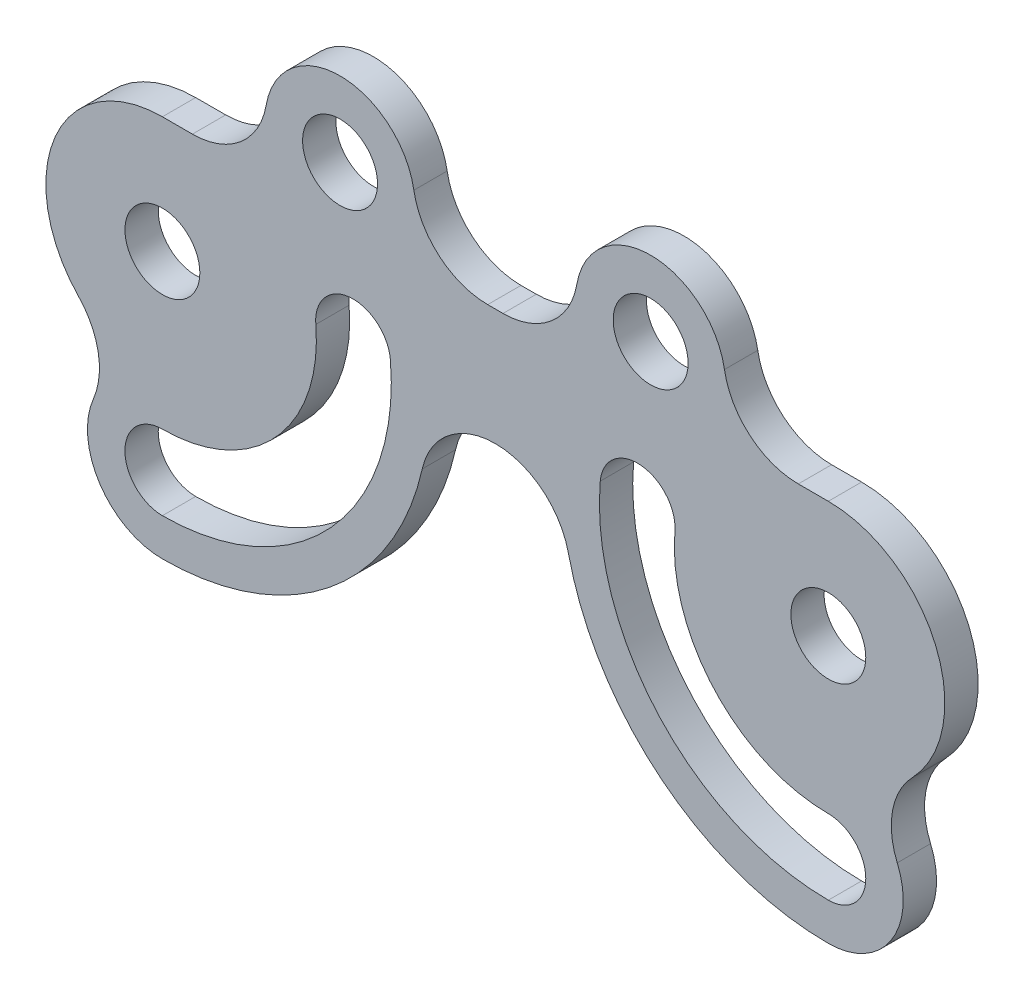
SolidWorks part; units mm, degrees
ref_plane "Front Plane" through (0, 0, 0) normal (0, 0, 1) x (1, 0, 0)
ref_plane "Top Plane" through (0, 0, 0) normal (0, 1, 0) x (1, 0, 0)
ref_plane "Right Plane" through (0, 0, 0) normal (1, 0, 0) x (0, 0, -1)
sketch "Sketch1" plane through (0, 0, 0) normal (0, 0, 1) x (1, 0, 0)
  line L14 (5.5562, 0) -> (26.1937, 0)
  line L15 (0, 5.5563) -> (31.75, 5.5563)
  line L16 (0, 5.5563) -> (0, -5.5563) construction
  line L17 (0, -5.5563) -> (31.75, -5.5563) construction
  line L18 (31.75, 5.5563) -> (31.75, -5.5563) construction
  line L19 (0, 5.5563) -> (31.75, 5.5563) construction
  line L20 (31.75, 0) -> (22.6566, 0.7956) construction
  line L21 (0, 0) -> (9.0934, 0.7956) construction
  line L22 (9.0934, 0.7956) -> (8.4708, 7.9121) construction
  line L23 (22.6566, 0.7956) -> (23.2792, 7.9121) construction
  circle A46 centre (0, 0) radius 5.5563 construction
  circle A47 centre (31.75, 0) radius 5.5563 construction
  arc A48 (0, 5.5563) -> (0, -5.5563) centre (0, 0) ccw
  arc A49 (31.75, -5.5563) -> (31.75, 5.5563) centre (31.75, 0) ccw
  circle A50 centre (0, 0) radius 1.7859
  circle A51 centre (31.75, 0) radius 1.7859
  arc A52 (0, -5.5563) -> (5.5562, 0) centre (0, 0) ccw
  arc A53 (26.1937, 0) -> (31.75, -5.5563) centre (31.75, 0) ccw
  circle A54 centre (31.75, 0) radius 9.1281 construction
  circle A55 centre (0, 0) radius 9.1281 construction
  circle A56 centre (31.75, -9.1281) radius 3.5719
  circle A57 centre (0, -9.1281) radius 3.5719
  circle A58 centre (0, -9.1281) radius 1.7859
  circle A59 centre (8.4708, 7.9121) radius 1.7859
  circle A60 centre (8.4708, 7.9121) radius 3.5719
  circle A61 centre (9.0934, 0.7956) radius 1.7859
  circle A62 centre (9.0934, 0.7956) radius 3.5719 construction
  circle A63 centre (22.6566, 0.7956) radius 1.7859
  circle A64 centre (22.6566, 0.7956) radius 3.5719 construction
  circle A65 centre (23.2792, 7.9121) radius 1.7859
  circle A66 centre (23.2792, 7.9121) radius 3.5719
  circle A67 centre (31.75, -9.1281) radius 1.7859
  arc A68 (7.3142, 0.6399) -> (0, -7.3422) centre (0, 0) cw
  arc A69 (0, -12.7) -> (12.6517, 1.1069) centre (0, 0) ccw
  arc A70 (0, -10.9141) -> (10.8725, 0.9512) centre (0, 0) ccw
  arc A71 (24.4358, 0.6399) -> (31.75, -7.3422) centre (31.75, 0) ccw
  arc A72 (20.8775, 0.9512) -> (31.75, -10.9141) centre (31.75, 0) ccw
  arc A73 (19.0983, 1.1069) -> (31.75, -12.7) centre (31.75, 0) ccw
  point P0 (8.0396, 0.6156)
  dimension "D9" = 3.5719
  dimension "D10" = 31.75
  dimension "D13" = 7.1437
  dimension "D11" = 11.1125
  dimension "D12" = 95
  dimension "D14" = 95
extrude "Boss-Extrude1" add sketch "Sketch1" along normal blind 1.5875 contours A72 A63 A71 L14 A53 A49 L15 A66 A60 A48 A52 A68 A61 A70 A50 A51 | A70 A58 A68 A57 | A72 A56 A71 A67 | L14 A73 A56 A72 | L14 A71 A56 A53 | A70 A57 A69 L14 | A68 L14 A52 A57 | L15 A60 A59 | L15 A66 A65 | L15 A66 | L15 A60 region at (15.875, 1.1263, 0) region at (4.8327, -3.5918, 0) region at (1.4594, -5.9772, 0) region at (8.4862, -6.9106, 0) region at (7.2448, 11.168, 0) region at (8.4708, 5.062, 0) region at (23.2638, -6.9106, 0) region at (22.0533, 11.168, 0) region at (23.2792, 5.062, 0) region at (29.7754, -11.9845, 0) region at (26.9173, -3.5918, 0)
fillet "Fillet1" radius 3.5719 8 edges at (31.75, -5.5563, 0.7937) (19.05, 0, 0.7937) (12.7, 0, 0.7937) (0, -5.5563, 0.7937) (25.964, 5.5563, 0.7937) (11.1556, 5.5563, 0.7937) (20.5944, 5.5563, 0.7937) (5.786, 5.5563, 0.7937)
